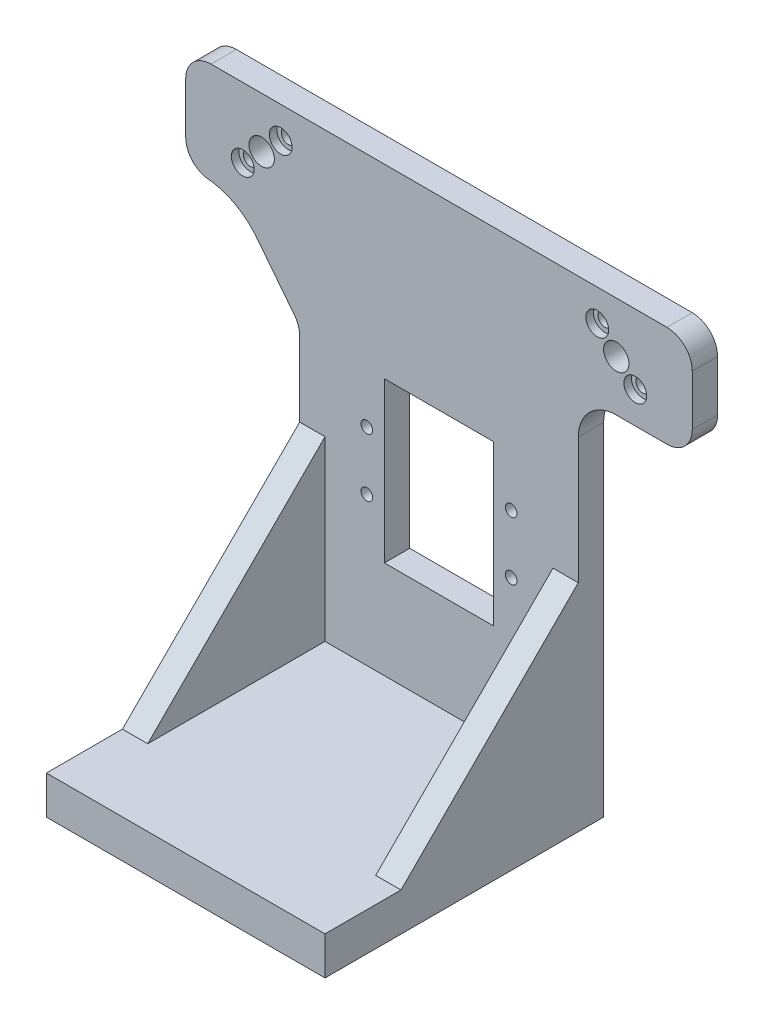
SolidWorks part; units mm, degrees
ref_plane "Ebene vorne" through (0, 0, 0) normal (0, 0, 1) x (1, 0, 0)
ref_plane "Ebene oben" through (0, 0, 0) normal (0, 1, 0) x (1, 0, 0)
ref_plane "Ebene rechts" through (0, 0, 0) normal (1, 0, 0) x (0, 0, -1)
sketch "Skizze1" plane through (0, 0, 0) normal (0, 0, 1) x (1, 0, 0)
  line L0 (0, 0) -> (0, 120.8446) construction
  line L1 (0, 120.8446) -> (0, -115.4537) construction
  line L2 (-21.55, 2.2046) -> (-75.2531, 2.2046) construction
  line L15 (90, 107.0546) -> (-90, 107.0546)
  line L16 (-100, 97.0546) -> (-100, 77.0546)
  line L17 (-90, 67.0546) -> (-70, 67.0546)
  line L18 (-55, 52.0546) -> (-55, -82.9454)
  line L21 (-55, -82.9454) -> (55, -82.9454)
  line L24 (55, 52.0546) -> (55, -82.9454)
  line L25 (90, 67.0546) -> (70, 67.0546)
  line L26 (100, 97.0546) -> (100, 77.0546)
  line L27 (21.55, 33.7046) -> (-21.55, 33.7046)
  line L28 (-21.55, 33.7046) -> (-21.55, -29.2954)
  line L29 (-21.55, -29.2954) -> (21.55, -29.2954)
  line L30 (-28.5, 26.717) -> (-28.5, -23.7709) construction
  line L31 (21.55, 33.7046) -> (21.55, -29.2954)
  line L32 (-152.8572, 87.0546) -> (12.8572, 87.0546) construction
  line L33 (-62.5, 94.5546) -> (-83.4096, 94.5546) construction
  line L34 (-77.5, 79.5546) -> (-83.4096, 79.5546) construction
  line L35 (-62.5, 94.5546) -> (-62.5, 69.0538) construction
  line L36 (-77.5, 79.5546) -> (-77.5, 100.8525) construction
  line L37 (-21.55, 2.2046) -> (21.55, 2.2046) construction
  arc A0 (-100, 77.0546) -> (-90, 67.0546) centre (-90, 77.0546) ccw
  arc A1 (-90, 107.0546) -> (-100, 97.0546) centre (-90, 97.0546) ccw
  arc A2 (-70, 67.0546) -> (-55, 52.0546) centre (-70, 52.0546) cw
  arc A3 (70, 67.0546) -> (55, 52.0546) centre (70, 52.0546) ccw
  arc A4 (90, 107.0546) -> (100, 97.0546) centre (90, 97.0546) cw
  arc A5 (100, 77.0546) -> (90, 67.0546) centre (90, 77.0546) cw
  circle A6 centre (-28.5, 13.7046) radius 2.3
  circle A7 centre (-28.5, -9.2954) radius 2.3
  circle A8 centre (28.5, -9.2954) radius 2.3
  circle A9 centre (28.5, 13.7046) radius 2.3
  circle A10 centre (-70, 87.0546) radius 5
  circle A11 centre (-62.5, 94.5546) radius 2.75
  circle A12 centre (-77.5, 79.5546) radius 2.75
  circle A13 centre (77.5, 79.5546) radius 2.75
  circle A14 centre (62.5, 94.5546) radius 2.75
  circle A15 centre (70, 87.0546) radius 5
  point P12 (-54.2543, -67.9454)
  point P18 (-100, 107.0546)
  point P22 (0, 107.0546)
  point P23 (0, -82.9454)
  point P33 (100, 107.0546)
  point P50 (0, -29.2954)
  point P51 (0, 33.7046)
  dimension "D7" = 10
  dimension "D8" = 15
  dimension "D11" = 4.6
  dimension "D12" = 4.6
  dimension "D15" = 10
  dimension "D16" = 5.5
  dimension "D17" = 5.5
  dimension "D1" = 100
  dimension "D2" = 55
  dimension "D4" = 40
  dimension "D9" = 63
  dimension "D10" = 21.55
  dimension "D13" = 28.5
  dimension "D14" = 23
  dimension "D18" = 7.5
  dimension "D19" = 7.5
  dimension "D20" = 7.5
  dimension "D21" = 7.5
  dimension "D22" = 20
  dimension "D23" = 140
  dimension "D24" = 84.85
  dimension "D3" = 150
extrude "Aufsatz-Linear austragen1" add sketch "Skizze1" along normal blind 10
sketch "Skizze2" plane through (0, 0, 10) normal (0, 0, 1) x (1, 0, 0)
  line L0 (-21.55, 2.2046) -> (21.55, 2.2046) construction
  line L1 (-21.55, 33.7046) -> (-21.55, -29.2954) construction
  line L2 (21.55, -29.2954) -> (21.55, 33.7046) construction
  line L3 (0, 33.7046) -> (0, -29.2954) construction
  line L4 (21.55, 33.7046) -> (-21.55, 33.7046) construction
  line L5 (-21.55, -29.2954) -> (21.55, -29.2954) construction
  line L6 (-70, 92.0546) -> (-70, 82.0546) construction
  line L7 (-65, 87.0546) -> (-75, 87.0546) construction
  line L8 (-13.4991, -8.9319) -> (-83.4991, 75.9181)
  line L9 (-56.5009, 98.1912) -> (13.4991, 13.3412)
  circle A0 centre (-70, 87.0546) radius 5 construction
  circle A1 centre (0, 2.2046) radius 17.5
  circle A2 centre (-70, 87.0546) radius 17.5
  point P27 (0, 0)
  dimension "D1" = 35
  dimension "D2" = 35
sketch "Skizze3" plane through (0, 0, 10) normal (0, 0, 1) x (1, 0, 0)
  line L0 (-90, 67.0546) -> (-70, 67.0546) construction
  line L1 (-72.8459, 57.8146) -> (-56.7743, 37.3523)
  line L2 (-55, 52.0546) -> (-55, -82.9454) construction
  line L3 (-55, 18.961) -> (-43.3334, 21.2005)
  line L4 (-43.3334, 21.2005) -> (-45.498, 67.0546)
  line L5 (-45.498, 67.0546) -> (-90, 67.0546)
  arc A0 (-100, 77.0546) -> (-90, 67.0546) centre (-90, 77.0546) ccw construction
  spline S0 degree 2 poles (-90, 67.0546) (-79.9383, 65.6564) (-72.8459, 57.8146) knots 0 0 0 1 1 1
  spline S1 degree 2 poles (-55, 18.961) (-46.6365, 27.9631) (-56.7743, 37.3523) knots 0 0 0 1 1 1
  point P8 (-77.8994, 63.0337)
  point P13 (-52.135, 29.565)
  point P14 (-50, 18.961)
  point P15 (-91.0594, 67.1109)
  point P19 (-83.6984, 65.4362)
  point P20 (-51.3066, 25.9199)
  point P21 (-72.8459, 57.8146)
  point P22 (-56.7743, 37.3523)
extrude "Aufsatz-Linear austragen3" add sketch "Skizze3" against normal blind 10
sketch "Skizze4" plane through (0, 0, 10) normal (0, 0, 1) x (1, 0, 0)
  line L0 (55, -82.9454) -> (55, 52.0546) construction
  line L1 (-55, -67.8557) -> (55, -67.8557)
  line L2 (-55, -67.8557) -> (-55, -82.9454)
  line L3 (-55, -82.9454) -> (55, -82.9454)
  line L4 (55, -67.8557) -> (55, -82.9454)
  line L5 (-55, 35.555) -> (-55, -82.9454) construction
  point P6 (0, 0)
  point P7 (55, -82.9454)
  point P9 (55, -67.9454)
  point P12 (-60, -67.9454)
  point P13 (-55, -67.8557)
  point P16 (-55, -82.9454)
extrude "Aufsatz-Linear austragen4" add sketch "Skizze4" along normal blind 100
sketch "Skizze6" plane through (-55, 0, 0) normal (-1, 0, 0) x (0, 0, 1)
  line L5 (60.1366, -67.0551) -> (60.1366, -66.9447)
fillet "Verrundung5" radius 10 1 edges at (-55, 35.555, 5)
sketch "Skizze11" plane through (0, 0, 10) normal (0, 0, 1) x (1, 0, 0)
  circle A0 centre (62.5, 94.5546) radius 4.5
  circle A2 centre (77.5, 79.5546) radius 4.5
  circle A3 centre (-62.5, 94.5546) radius 4.5
  circle A4 centre (-77.5, 79.5546) radius 4.5
  dimension "D1" = 9
  dimension "D2" = 9
  dimension "D3" = 9
  dimension "D4" = 9
extrude "Schnitt-Linear austragen1" cut sketch "Skizze11" against normal blind 3
sketch "Skizze12" plane through (0, 0, 0) normal (0, 0, -1) x (-1, 0, 0)
  line L0 (26.2, 13.7046) -> (30.8, 13.7046) construction
  line L1 (28.5, 16.0046) -> (28.5, 11.4046) construction
  line L2 (28.5, 16.0046) -> (28.5, 17.7471) construction
  line L3 (28.5, 11.4046) -> (28.5, 9.6621) construction
  line L4 (28.5, 17.7471) -> (24.825, 15.7871)
  line L5 (24.825, 15.7871) -> (24.825, 11.6221)
  line L6 (24.825, 11.6221) -> (28.5, 9.6621)
  line L7 (32.175, 11.6221) -> (28.5, 9.6621)
  line L8 (32.175, 15.7871) -> (32.175, 11.6221)
  line L9 (28.5, 17.7471) -> (32.175, 15.7871)
  line L10 (26.2, -9.2954) -> (30.8, -9.2954) construction
  line L11 (28.5, -6.9954) -> (28.5, -11.5954) construction
  line L12 (28.5, -6.9954) -> (28.5, -5.2529) construction
  line L13 (28.5, -11.5954) -> (28.5, -13.3379) construction
  line L14 (28.5, -5.2529) -> (24.825, -7.2129)
  line L15 (24.825, -7.2129) -> (24.825, -11.3779)
  line L16 (24.825, -11.3779) -> (28.5, -13.3379)
  line L17 (32.175, -11.3779) -> (28.5, -13.3379)
  line L18 (32.175, -7.2129) -> (32.175, -11.3779)
  line L19 (28.5, -5.2529) -> (32.175, -7.2129)
  line L20 (-30.8, -9.2954) -> (-26.2, -9.2954) construction
  line L21 (-28.5, -6.9954) -> (-28.5, -11.5954) construction
  line L22 (-28.5, -6.9954) -> (-28.5, -5.2529) construction
  line L23 (-28.5, -11.5954) -> (-28.5, -13.3379) construction
  line L24 (-28.5, -5.2529) -> (-32.175, -7.2129)
  line L25 (-32.175, -7.2129) -> (-32.175, -11.3779)
  line L26 (-32.175, -11.3779) -> (-28.5, -13.3379)
  line L27 (-24.825, -11.3779) -> (-28.5, -13.3379)
  line L28 (-24.825, -7.2129) -> (-24.825, -11.3779)
  line L29 (-28.5, -5.2529) -> (-24.825, -7.2129)
  line L30 (-30.8, 13.7046) -> (-26.2, 13.7046) construction
  line L31 (-28.5, 16.0046) -> (-28.5, 11.4046) construction
  line L32 (-28.5, 16.0046) -> (-28.5, 17.7471) construction
  line L33 (-28.5, 11.4046) -> (-28.5, 9.6621) construction
  line L34 (-28.5, 17.7471) -> (-32.175, 15.7871)
  line L35 (-32.175, 15.7871) -> (-32.175, 11.6221)
  line L36 (-32.175, 11.6221) -> (-28.5, 9.6621)
  line L37 (-24.825, 11.6221) -> (-28.5, 9.6621)
  line L38 (-24.825, 15.7871) -> (-24.825, 11.6221)
  line L39 (-28.5, 17.7471) -> (-24.825, 15.7871)
  circle A0 centre (28.5, 13.7046) radius 2.3 construction
  circle A1 centre (28.5, -9.2954) radius 2.3 construction
  circle A2 centre (-28.5, -9.2954) radius 2.3 construction
  circle A3 centre (-28.5, 13.7046) radius 2.3 construction
  point P7 (26.2, -9.2954)
  point P14 (30.8, -9.2954)
  point P15 (28.5, -6.9954)
  point P16 (28.5, -11.5954)
  point P17 (28.5, -6.9954)
  point P18 (28.5, -11.5954)
  point P19 (26.2, -9.2954)
  point P32 (0, 0)
  point P33 (0, 0)
  point P34 (0, 0)
  point P35 (0, 0)
  point P56 (-26.2, -9.2954)
  point P59 (-30.8, -9.2954)
  point P60 (-28.5, -6.9954)
  point P61 (-28.5, -11.5954)
  point P62 (-28.5, 16.0046)
  point P65 (-26.2, 13.7046)
  point P66 (-30.8, 13.7046)
  point P67 (-28.5, 11.4046)
  dimension "D1" = 8.085
  dimension "D2" = 3.675
  dimension "D3" = 8.085
  dimension "D4" = 3.675
  dimension "D5" = 8.085
  dimension "D6" = 3.675
  dimension "D7" = 8.085
  dimension "D8" = 3.675
extrude "Schnitt-Linear austragen2" cut sketch "Skizze12" against normal blind 3
sketch "Skizze15" plane through (-55, 0, 0) normal (-1, 0, 0) x (0, 0, 1)
  line L0 (10, 2.1443) -> (80, -67.8557)
  line L1 (10, 33.7046) -> (10, -29.2954) construction
  line L2 (110, -67.8557) -> (10, -67.8557) construction
  line L3 (80, -67.8557) -> (10, -67.8557)
  line L4 (10, -67.8557) -> (10, 2.1443)
  dimension "D1" = 70
  dimension "D2" = 70
extrude "Aufsatz-Linear austragen7" add sketch "Skizze15" against normal blind 10
sketch "Skizze16" plane through (55, 0, 0) normal (1, 0, 0) x (0, 0, -1)
  line L0 (-10, 2.2046) -> (-80, -67.8557)
  line L1 (-10, 19.7046) -> (-10, -15.2954) construction
  line L2 (-80, -67.8557) -> (-10, -67.8557)
  line L3 (-10, -67.8557) -> (-10, 2.2046)
extrude "Aufsatz-Linear austragen8" add sketch "Skizze16" against normal blind 10
equation "\"D10@Skizze1\"=43.1/2"
equation "\"D13@Skizze1\"=57/2"
